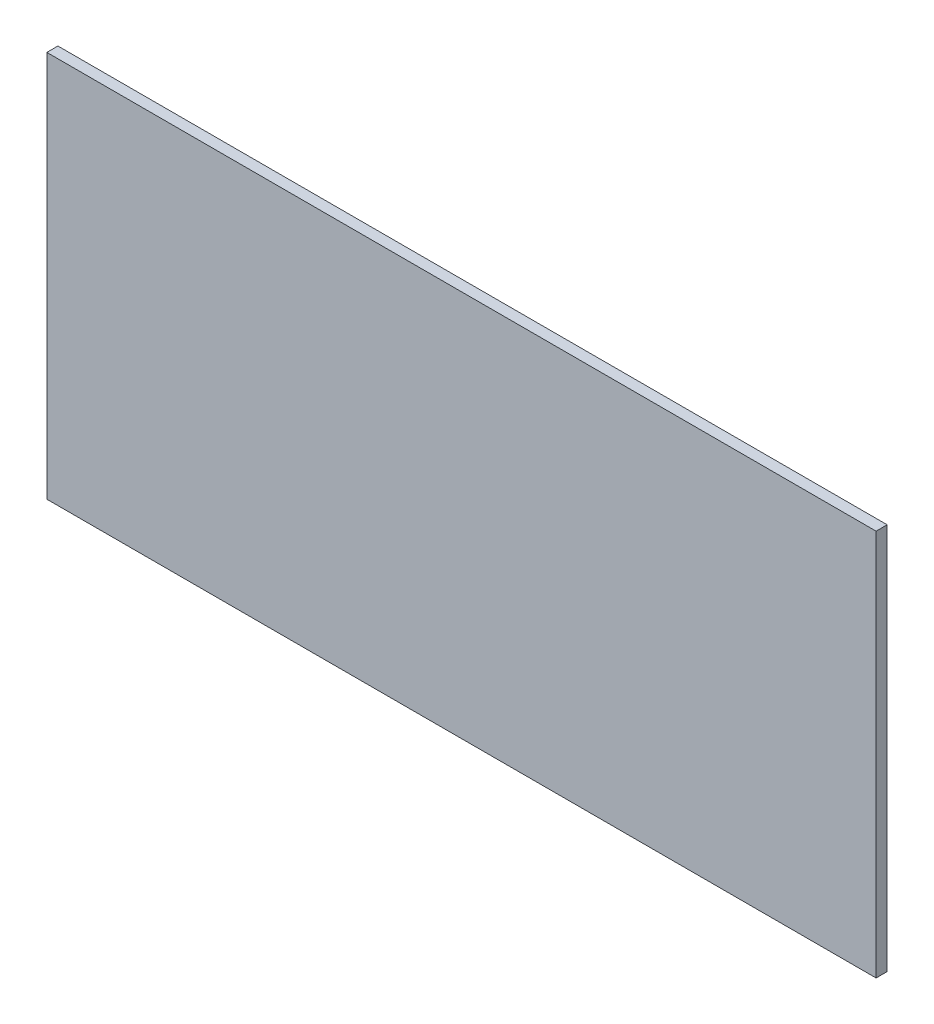
SolidWorks part; units mm, degrees
material "Brass"
ref_plane "Front Plane" through (0, 0, 0) normal (0, 0, 1) x (1, 0, 0)
ref_plane "Top Plane" through (0, 0, 0) normal (0, 1, 0) x (1, 0, 0)
ref_plane "Right Plane" through (0, 0, 0) normal (1, 0, 0) x (0, 0, -1)
sketch "Sketch1" plane through (0, 0, 0) normal (0, 0, 1) x (1, 0, 0)
  line L0 (0, 0) -> (300, 0)
  line L1 (300, 0) -> (300, 140)
  line L2 (300, 140) -> (0, 140)
  line L3 (0, 140) -> (0, 0)
  dimension "D1" = 300
  dimension "D2" = 140
extrude "Boss-Extrude1" add sketch "Sketch1" along normal blind 4
sketch "Sketch2" plane through (0, 0, 0) normal (0, 0, 1) x (1, 0, 0)
  circle A0 centre (15, 15) radius 1.5
  circle A1 centre (15, 124) radius 1.5
  circle A2 centre (287, 15) radius 1.5
  circle A3 centre (287, 124) radius 1.5
  dimension "D3" = 3
  dimension "D6" = 3
  dimension "D9" = 3
  dimension "D12" = 3
  dimension "D1" = 15
  dimension "D2" = 15
  dimension "D4" = 15
  dimension "D5" = 124
  dimension "D7" = 287
  dimension "D8" = 15
  dimension "D10" = 287
  dimension "D11" = 124
extrude "Cut-Extrude1" cut sketch "Sketch2" against normal mid plane 7
